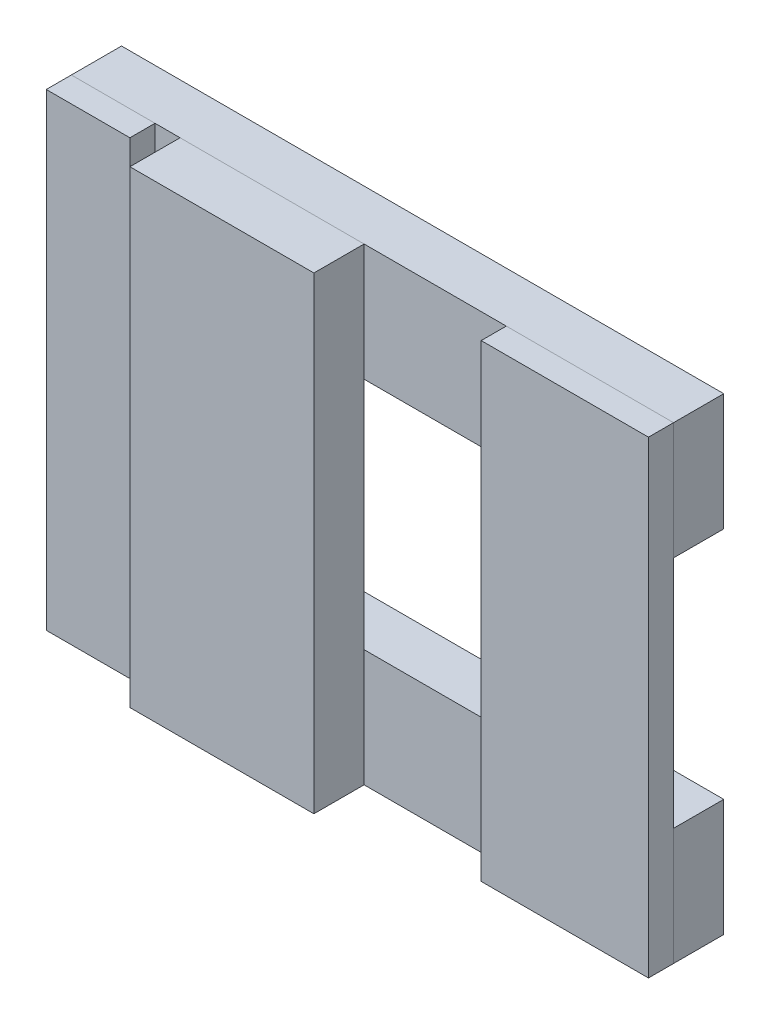
SolidWorks part; units mm, degrees
ref_plane "Front Plane" through (0, 0, 0) normal (0, 0, 1) x (1, 0, 0)
ref_plane "Top Plane" through (0, 0, 0) normal (0, 1, 0) x (1, 0, 0)
ref_plane "Right Plane" through (0, 0, 0) normal (1, 0, 0) x (0, 0, -1)
sketch "Sketch1" plane through (0, 0, 0) normal (0, 1, 0) x (1, 0, 0)
  line L0 (0, 0) -> (0, 78.573) construction
  line L1 (-158.75, 304.8) -> (-69.85, 304.8)
  line L2 (-158.75, 304.8) -> (-158.75, -304.8)
  line L3 (-158.75, -304.8) -> (-69.85, -304.8)
  line L4 (-69.85, 304.8) -> (-69.85, -304.8)
  line L5 (69.85, 304.8) -> (69.85, -304.8)
  line L6 (158.75, -304.8) -> (69.85, -304.8)
  line L7 (158.75, 304.8) -> (158.75, -304.8)
  line L8 (158.75, 304.8) -> (69.85, 304.8)
  line L9 (69.85, 0) -> (0, 0) construction
  line L10 (0, 0) -> (-69.85, 0) construction
  line L12 (-69.85, 177.8) -> (69.85, 177.8)
  line L13 (-69.85, 177.8) -> (-69.85, -6.03)
  line L14 (-69.85, -6.03) -> (69.85, -6.03)
  line L15 (69.85, 177.8) -> (69.85, -6.03)
  point P4 (-69.85, 0)
  dimension "D1" = 88.9
  dimension "D2" = 609.6
  dimension "D3" = 139.7
  dimension "D4" = 183.83
  dimension "D5" = 127
sketch "Sketch2" plane through (0, 0, 0) normal (0, 0, 1) x (1, 0, 0)
  line L0 (0, 0) -> (154.653, 0) construction
  line L1 (-217.6617, 177.8) -> (239.5383, 177.8)
  line L2 (-217.6617, 177.8) -> (-217.6617, 88.9)
  line L3 (-217.6617, 88.9) -> (239.5383, 88.9)
  line L4 (239.5383, 177.8) -> (239.5383, 88.9)
  line L5 (-217.6617, -88.9) -> (239.5383, -88.9)
  line L6 (239.5383, -177.8) -> (239.5383, -88.9)
  line L7 (-217.6617, -177.8) -> (239.5383, -177.8)
  line L8 (-217.6617, -177.8) -> (-217.6617, -88.9)
  dimension "D1" = 457.2
  dimension "D2" = 88.9
  dimension "D3" = 355.6
extrude "Boss-Extrude1" add sketch "Sketch2" along normal blind 38.1
sketch "Sketch3" plane through (0, 0, 38.1) normal (0, 0, 1) x (1, 0, 0)
  line L0 (239.5383, 177.8) -> (-217.6617, 177.8) construction
  line L1 (-135.1117, 177.8) -> (4.5883, 177.8)
  line L2 (-135.1117, 177.8) -> (-135.1117, -177.8)
  line L3 (-135.1117, -177.8) -> (4.5883, -177.8)
  line L4 (4.5883, 177.8) -> (4.5883, -177.8)
  line L5 (-217.6617, -177.8) -> (239.5383, -177.8) construction
  line L6 (239.5383, 88.9) -> (239.5383, 177.8) construction
  line L8 (-217.6617, 177.8) -> (-154.1617, 177.8)
  line L9 (-217.6617, 177.8) -> (-217.6617, -177.8)
  line L10 (-217.6617, -177.8) -> (-154.1617, -177.8)
  line L11 (-154.1617, 177.8) -> (-154.1617, -177.8)
  line L12 (239.5383, 177.8) -> (112.5383, 177.8)
  line L13 (239.5383, 177.8) -> (239.5383, -177.8)
  line L14 (239.5383, -177.8) -> (112.5383, -177.8)
  line L15 (112.5383, 177.8) -> (112.5383, -177.8)
  line M14 (-217.6617, 88.9) -> (239.5383, 88.9)
  line M15 (239.5383, 88.9) -> (239.5383, 177.8)
  line M16 (239.5383, 177.8) -> (-217.6617, 177.8)
  dimension "D1" = 139.7
  dimension "D2" = 234.95
  dimension "D3" = 63.5
  dimension "D4" = 127
extrude "Boss-Extrude2" add sketch "Sketch3" along normal blind 19.05 separate body contours L15 L14 L13 M14 | L15 M16 M14 M15 | L11 L10 L9 L8 region at (176.0383, 133.35, 38.1) region at (176.0383, -44.45, 38.1)
extrude "Boss-Extrude3" add sketch "Sketch3<3>" along normal blind 38.1 separate body contours L4 L3 L2 L1
sketch "Sketch3<3>" plane through (0, 0, 38.1) normal (0, 0, 1) x (1, 0, 0) same geometry as "Sketch3"
